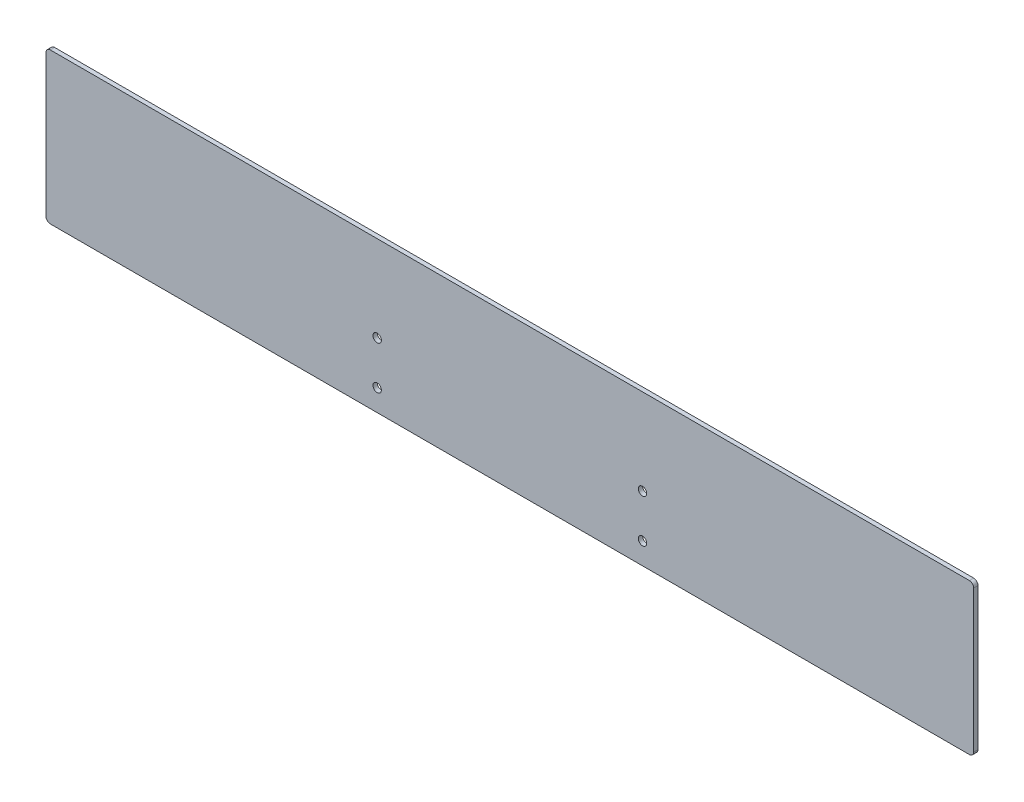
SolidWorks part; units mm, degrees
ref_plane "Front Plane" through (0, 0, 0) normal (0, 0, 1) x (1, 0, 0)
ref_plane "Top Plane" through (0, 0, 0) normal (0, 1, 0) x (1, 0, 0)
ref_plane "Right Plane" through (0, 0, 0) normal (1, 0, 0) x (0, 0, -1)
sketch "Sketch1" plane through (0, 0, 0) normal (0, 0, 1) x (1, 0, 0)
  line L1 (-356.9059, 25.5535) -> (73.0941, 25.5535)
  line L2 (-356.9059, 25.5535) -> (-356.9059, -44.2965)
  line L3 (-356.9059, -44.2965) -> (73.0941, -44.2965)
  line L4 (73.0941, 25.5535) -> (73.0941, -44.2965)
  circle A0 centre (-80.4059, -14.2965) radius 1.95
  circle A1 centre (-80.4059, -34.2965) radius 1.95
  circle A2 centre (-203.4059, -14.2965) radius 1.95
  circle A3 centre (-203.4059, -34.2965) radius 1.95
  dimension "D3" = 123
  dimension "D4" = 20
  dimension "D1" = 430
  dimension "D2" = 69.85
  dimension "D5" = 10
  dimension "D6" = 153.5
extrude "Boss-Extrude1" add sketch "Sketch1" along normal blind 2
fillet "Fillet1" radius 2 4 edges at (73.0941, 25.5535, 1) (73.0941, -44.2965, 1) (-356.9059, -44.2965, 1) (-356.9059, 25.5535, 1)
